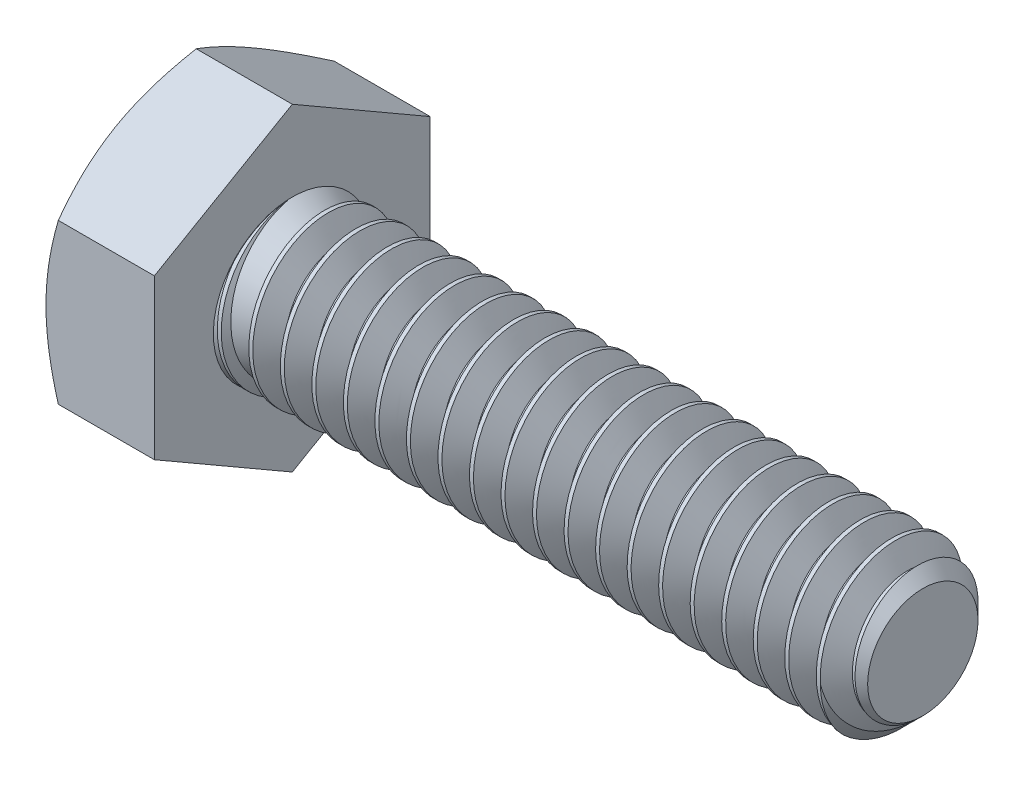
SolidWorks part; units mm, degrees
note: '?' marks a value the reader was unsure of.
ref_plane "Front Plane" through (0, 0, 0) normal (0, 0, 1) x (1, 0, 0)
ref_plane "Top Plane" through (0, 0, 0) normal (0, 1, 0) x (1, 0, 0)
ref_plane "Right Plane" through (0, 0, 0) normal (1, 0, 0) x (0, 0, -1)
sketch "Sketch1" plane through (0, 0, 0) normal (0, 0, 1) x (1, 0, 0)
  line L0 (-14.8828, 0) -> (14.8828, 0) construction
  line L1 (14.8828, 3.175) -> (14.8828, -3.175) construction
  line L2 (-10.5172, 5.5562) -> (-10.5172, -5.5562) construction
  line L3 (-14.8828, 5.5562) -> (-14.8828, -5.5562) construction
  line L4 (-10.7712, 3.1812) -> (-10.5172, 3.1812) construction
  line L5 (-10.5172, 3.1812) -> (-5.0071, 0) construction
  line L6 (-10.7712, 3.1812) -> (-10.7712, 0) construction
  line L7 (-10.5172, 0) -> (-10.5172, 3.1812) construction
  point P9 (-10.5172, 0)
  point P10 (10.4378, -3.175)
  dimension "Screw Dia" = 6.35
  dimension "Hex" = 11.1125
  dimension "Head Ht" = 4.3656
  dimension "Screw Length" = 25.4
  dimension "D1" = 4.445
  dimension "D2" = 30
  dimension "D3" = 0.254
  dimension "MinThread" = 25.4
  dimension "D4" = 0.0124
ref_plane "Plane2" through (14.8828, 0, 0) normal (1, 0, 0) x (0, 0, -1)
sketch "Sketch5" plane through (14.8828, 0, 0) normal (1, 0, 0) x (0, 0, -1)
  circle A0 centre (0, 0) radius 3.175
extrude "Boss-Extrude3" add sketch "Sketch5" against normal up to vertex (25.4 mm away) up to point (-10.5172, 0, 0)
sketch "Sketch9" plane through (14.8828, 0, 0) normal (1, 0, 0) x (0, 0, -1)
  circle A1 centre (0, 0) radius 3.175
  circle A2 centre (0, 0) radius 3.175
  dimension "D1" = 0
chamfer "Chamfer1" distance 0.9525 angle 45 1 edges at (14.8828, 0, -3.175)
sketch "Sketch6" plane through (-10.5172, 0, 0) normal (-1, 0, 0) x (0, 0, 1)
  line L0 (0, 5.5562) -> (0, -5.5562) construction
  line L1 (5.5563, 3.2079) -> (0, 6.4158)
  line L2 (0, 6.4158) -> (-5.5562, 3.2079)
  line L3 (-5.5562, 3.2079) -> (-5.5562, -3.2079)
  line L4 (-5.5562, -3.2079) -> (0, -6.4158)
  line L5 (0, -6.4158) -> (5.5563, -3.2079)
  line L6 (5.5563, -3.2079) -> (5.5563, 3.2079)
  circle A0 centre (0, 0) radius 5.5562 construction
extrude "Boss-Extrude4" add sketch "Sketch6" along normal up to vertex (4.3656 mm away) separate body up to point (-14.8828, -5.5562, 0)
sketch "Sketch7" plane through (-14.8828, 0, 0) normal (-1, 0, 0) x (0, 0, 1)
  circle A0 centre (0, 0) radius 5.5562 construction
  circle A1 centre (0, 0) radius 5.5562
sketch "Sketch8" plane through (-14.8828, 0, 0) normal (-1, 0, 0) x (0, 0, 1)
  circle A0 centre (0, 0) radius 5.5562 construction
  circle A1 centre (0, 0) radius 5.5562
extrude "Cut-Extrude3" cut sketch "Sketch8" against normal through all draft 60 flip side to cut
sketch "Sketch12" plane through (-14.8828, 0, 0) normal (-1, 0, 0) x (0, 0, 1)
  line L0 (0, 4.2783) -> (0, 2.3892) construction
  line L1 (0.1667, 4.2783) -> (0.1667, 2.3892)
  line L2 (-0.1667, 4.2783) -> (-0.1667, 2.3892)
  line L3 (0, 3.175) -> (0, -3.175) construction
  arc A0 (0.1667, 4.2783) -> (-0.1667, 4.2783) centre (0, 4.2783) ccw
  arc A1 (-0.1667, 2.3892) -> (0.1667, 2.3892) centre (0, 2.3892) ccw
  circle A3 centre (0, 0) radius 2.2225 construction
  circle A4 centre (0, 0) radius 4.445 construction
  point P2 (0, 3.3337)
  dimension "D1" = 4.445
  dimension "D3" = 8.89
  dimension "D2" = 0.3334
extrude "Cut-Extrude4" cut sketch "Sketch12" against normal blind 0.254
pattern_circular "CirPattern1" count 6 over 360 about axis through (0, 0, 0) along (1, 0, 0) of "Cut-Extrude4"
curve "Helix/Spiral1" pitch 1.27 height 26.67 turns 21 parameters "Pitch"=1.27
sketch "Sketch10" plane through (0, 0, 0) normal (0, 0, 1) x (1, 0, 0)
  line L0 (14.8828, 3.175) -> (15.3591, 2.3501)
  line L1 (15.3591, 2.3501) -> (15.5178, 2.3501)
  line L2 (15.5178, 2.3501) -> (15.9941, 3.175)
  line L3 (14.8828, 3.175) -> (15.9941, 3.175)
  line L4 (15.4384, 3.175) -> (15.4384, 2.3501) construction
  line L5 (15.1209, 2.7626) -> (15.7559, 2.7626) construction
  dimension "D1" = 60
  dimension "D2" = 0.1588
  dimension "D3" = 0.635
sweep "Cut-Sweep1" cut profiles "Sketch10" path "Helix/Spiral1" align with end faces yes
sketch "Sketch13" plane through (0, 0, 0) normal (0, 0, 1) x (1, 0, 0)
  line L0 (-14.8828, 0) -> (14.8828, 0) construction
  line L1 (-10.5172, 3.1812) -> (-5.0071, 0) construction
  line L2 (-10.7712, 3.1812) -> (-10.5172, 3.1812) construction
  line L3 (-10.7712, 3.1812) -> (-10.7712, 0) construction
  line L4 (-10.7712, 0) -> (-5.0071, 0)
  line L5 (-10.5172, 3.1812) -> (-5.0071, 0)
  line L6 (-10.7712, 3.1812) -> (-10.5172, 3.1812)
  line L7 (-10.7712, 3.1812) -> (-10.7712, 0)
revolve "Revolve7" add sketch "Sketch13" angle 360 about L4
ref_axis "Center Axis 1" through (-10.5064, 0, 0) along (1, 0, 0)?
ref_plane "Contact Plane 1" through (-10.5172, 0, 0) normal (1, 0, 0) x (0, 0, -1)
equation "\"D2@Sketch10\" = \"Pitch@Helix/Spiral1\"*.125"
equation "\"D3@Sketch10\" = \"Pitch@Helix/Spiral1\"*.5"
equation "\"D3@Helix/Spiral1\" = \"Screw Length@Sketch1\" + \"Pitch@Helix/Spiral1\""
equation "\"D1@Chamfer1\" = \"Pitch@Helix/Spiral1\"*.75"
equation "\"D1@Sketch12\" = \"Hex@Sketch1\"*.4"
equation "\"D3@Sketch12\" = \"Hex@Sketch1\"*.8"
equation "\"D2@Sketch12\" = \"Hex@Sketch1\"*.03"
equation "\"D1@Sketch1\" = \"Pitch@Helix/Spiral1\"*3.5"
